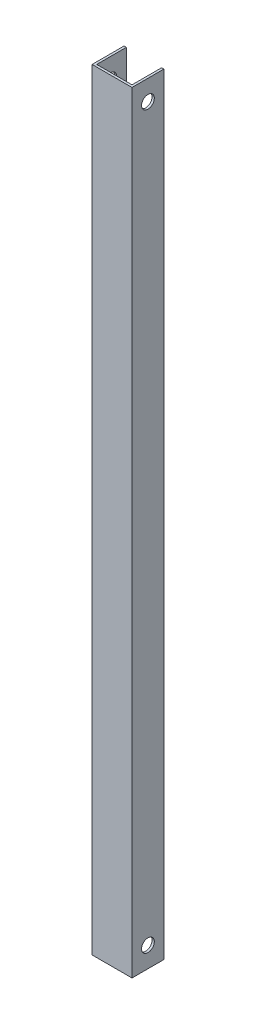
SolidWorks part; units mm, degrees
ref_plane "Front Plane" through (0, 0, 0) normal (0, 0, 1) x (1, 0, 0)
ref_plane "Top Plane" through (0, 0, 0) normal (0, 1, 0) x (1, 0, 0)
ref_plane "Right Plane" through (0, 0, 0) normal (1, 0, 0) x (0, 0, -1)
sketch "Sketch1" plane through (0, 0, 0) normal (0, 1, 0) x (1, 0, 0)
  line L1 (-7.5, 6) -> (7.5, 6)
  line L2 (-7.5, 6) -> (-7.5, -6)
  line L3 (-7.5, -6) -> (7.5, -6)
  line L4 (7.5, 6) -> (7.5, -6)
  line L5 (-7.5, 6) -> (7.5, -6) construction
  line L6 (-7.5, -6) -> (7.5, 6) construction
  point P0 (0, 0)
  dimension "D1" = 12
  dimension "D2" = 15
extrude "Boss-Extrude1" add sketch "Sketch1" along normal blind 145 and the other way blind 145
sketch "Sketch2" plane through (0, 0, 0) normal (0, 1, 0) x (1, 0, 0)
  line L0 (-6.64, 8.86) -> (-6.64, -5.14)
  line L1 (-6.64, -5.14) -> (6.64, -5.14)
  line L2 (6.64, -5.14) -> (6.64, 8.86)
  line L3 (6.64, 8.86) -> (-6.64, 8.86)
  line L4 (7.5, -6) -> (7.5, 6) construction
  line L5 (-7.5, 6) -> (-7.5, -6) construction
  line L6 (-7.5, -6) -> (7.5, -6) construction
  dimension "D1" = 0.86
  dimension "D2" = 0.86
  dimension "D3" = 0.86
  dimension "D4" = 14
extrude "Cut-Extrude1" cut sketch "Sketch2" against normal blind 200 and the other way blind 200
sketch "Sketch3" plane through (0, 0, 0) normal (1, 0, 0) x (0, 0, -1)
  line L0 (0, 137.33) -> (0, -137.33) construction
  circle A0 centre (0, 137.33) radius 2.4
  circle A1 centre (0, -137.33) radius 2.4
  dimension "D1" = 4.8
  dimension "D2" = 274.66
extrude "Cut-Extrude2" cut sketch "Sketch3" against normal blind 200 and the other way blind 200
